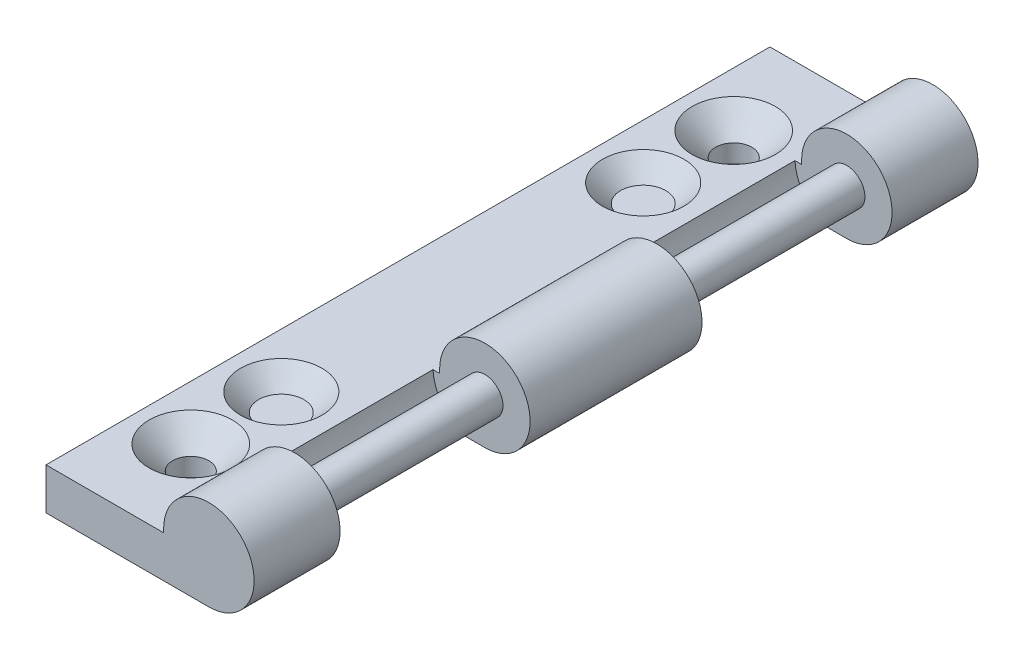
SolidWorks part; units mm, degrees
ref_plane "Front Plane" through (0, 0, 0) normal (0, 0, 1) x (1, 0, 0)
ref_plane "Top Plane" through (0, 0, 0) normal (0, 1, 0) x (1, 0, 0)
ref_plane "Right Plane" through (0, 0, 0) normal (1, 0, 0) x (0, 0, -1)
sketch "Sketch1" plane through (0, 0, 0) normal (0, 1, 0) x (1, 0, 0)
  line L1 (-9, 40) -> (0, 40)
  line L2 (-9, 40) -> (-9, 0)
  line L3 (-9, 0) -> (0, 0)
  line L4 (0, 40) -> (0, 0)
  dimension "D1" = 40
  dimension "D2" = 9
extrude "Boss-Extrude1" add sketch "Sketch1" along normal blind 2.5
sketch "Sketch2" plane through (0, 0, 0) normal (0, 0, 1) x (1, 0, 0)
  circle A0 centre (0, 2.5) radius 2.5
extrude "Boss-Extrude2" add sketch "Sketch2" against normal up to surface (40 mm away) up to face at (-4.5, 1.25, -40)
sketch "Sketch3" plane through (0, 0, 0) normal (0, 0, 1) x (1, 0, 0)
  circle A1 centre (0, 2.5) radius 2.875
  dimension "D1" = 5.75
extrude "Cut-Extrude1" cut sketch "Sketch3" against normal blind 10.5 from offset 4.75 offset against normal yes
ref_plane "Plane1" through (0, 0, -20) normal (0, 0, 1) x (1, 0, 0)
mirror "Mirror1" about plane through (0, 0, -20) normal (0, 0, 1) of "Cut-Extrude1"
sketch "Sketch4" plane through (0, 0, -15.25) normal (0, 0, 1) x (1, 0, 0)
  circle A0 centre (0, 2.5) radius 1
  dimension "D1" = 2
extrude "Boss-Extrude3" add sketch "Sketch4" along normal up to next
mirror "Mirror2" about plane through (0, 0, -20) normal (0, 0, 1) of "Boss-Extrude3"
sketch "Sketch5" plane through (0, 2.5, 0) normal (0, 1, 0) x (1, 0, 0)
  line L0 (-9, 0) -> (-2.5, 0) construction
  line L1 (-9, 40) -> (-9, 0) construction
  circle A0 centre (-6, 5) radius 1
  dimension "D1" = 2
  dimension "D2" = 5
  dimension "D3" = 3
extrude "Cut-Extrude2" cut sketch "Sketch5" against normal through all
mirror "Mirror3" about plane through (0, 0, -20) normal (0, 0, 1) of "Cut-Extrude2"
chamfer "Chamfer1" distance 1.5 angle 45 1 edges at (-6, 2.5, -4)
chamfer "Chamfer2" distance 1.5 angle 45 1 edges at (-6, 2.5, -36)
sketch "Sketch6" plane through (0, 0, 0) normal (0, 0, 1) x (1, 0, 0)
  line L3 (-9, 2.5) -> (-2.5, 2.5)
  line L4 (-9, 2.5) -> (-9, 2.3)
  line L5 (-9, 2.3) -> (-2.5, 2.3)
  line L6 (-2.5, 2.5) -> (-2.5, 2.3)
  dimension "D1" = 0.2
extrude "Cut-Extrude3" cut sketch "Sketch6" against normal through all
sketch "Sketch7" plane through (0, 2.3, 0) normal (0, 1, 0) x (1, 0, 0)
  line L0 (-6, 30) -> (-12.908, 30) construction
  line L1 (-6, 10) -> (-12.908, 10) construction
  line L2 (-6, 35) -> (-6, 5) construction
  circle A0 centre (-6, 30) radius 1.25
  circle A1 centre (-6, 10) radius 1.25
  dimension "D1" = 2.5
  dimension "D2" = 2.5
extrude "Cut-Extrude4" cut sketch "Sketch7" against normal blind 1
chamfer "Chamfer3" distance 1 angle 45 2 edges at (-6, 2.3, -8.75) (-6, 2.3, -28.75)
